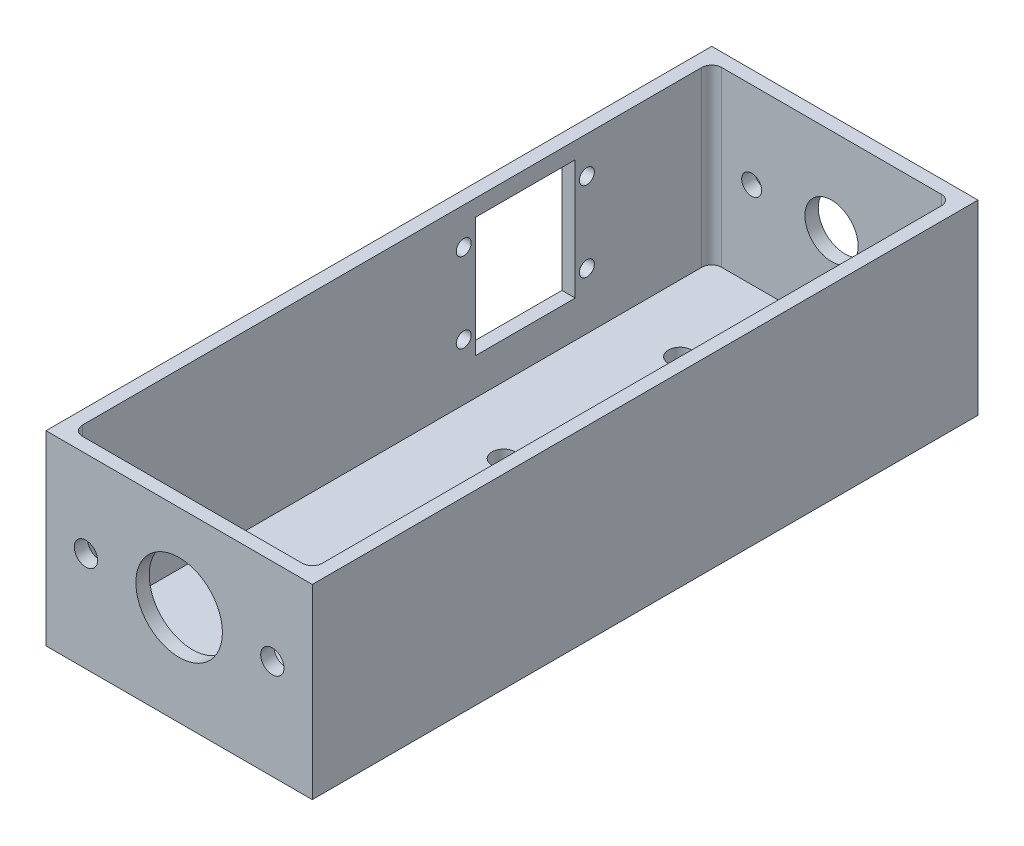
SolidWorks part; units mm, degrees
material "合金钢"
ref_plane "前视基准面" through (0, 0, 0) normal (0, 0, 1) x (1, 0, 0)
ref_plane "上视基准面" through (0, 0, 0) normal (0, 1, 0) x (1, 0, 0)
ref_plane "右视基准面" through (0, 0, 0) normal (1, 0, 0) x (0, 0, -1)
sketch "草图1" plane through (0, 0, 0) normal (0, 0, 1) x (1, 0, 0)
  line L1 (-40, -28) -> (40, -28)
  line L2 (-40, -28) -> (-40, 28)
  line L3 (-40, 28) -> (40, 28)
  line L4 (40, -28) -> (40, 28)
  line L5 (-40, -28) -> (40, 28) construction
  line L6 (-40, 28) -> (40, -28) construction
  point P0 (0, 0)
  dimension "D1" = 80
  dimension "D2" = 56
extrude "凸台-拉伸1" add sketch "草图1" against normal blind 200
sketch "草图2" plane through (0, 28, 0) normal (0, 1, 0) x (1, 0, 0)
  line L0 (-36, 193) -> (-36, 7)
  line L1 (-33, 4) -> (33, 4)
  line L2 (36, 7) -> (36, 193)
  line L3 (33, 196) -> (-33, 196)
  line L4 (-40, 0) -> (40, 0)
  line L5 (40, 0) -> (40, 200)
  line L6 (40, 200) -> (-40, 200)
  line L7 (-40, 200) -> (-40, 0)
  line L8 (-40, 0) -> (40, 0)
  line L9 (40, 0) -> (40, 200)
  line L10 (40, 200) -> (-40, 200)
  line L11 (-40, 200) -> (-40, 0)
  line L12 (-36, 4) -> (36, 4) construction
  line L13 (36, 4) -> (36, 196) construction
  line L14 (-36, 196) -> (-36, 4) construction
  line L15 (36, 196) -> (-36, 196) construction
  arc A0 (33, 4) -> (36, 7) centre (33, 7) ccw
  arc A1 (-36, 7) -> (-33, 4) centre (-33, 7) ccw
  arc A2 (36, 193) -> (33, 196) centre (33, 193) ccw
  arc A3 (-36, 193) -> (-33, 196) centre (-33, 193) cw
  dimension "D3" = 3
  dimension "D1" = 0
  dimension "D2" = 4
extrude "切除-拉伸1" cut sketch "草图2" against normal blind 52 contours A3 L0 A1 L1 A0 L2 A2 L3 region at (0, 28, -100)
sketch "草图3" plane through (0, 0, 0) normal (0, 0, 1) x (1, 0, 0)
  line L0 (0, 0) -> (0, 37.0041) construction
  line L4 (-40, -28) -> (40, -28) construction
  line L5 (40, 28) -> (-40, 28) construction
  line L9 (0, 2) -> (0, 28) construction
  line L10 (-28, 2) -> (28, 2) construction
  circle A0 centre (-28, 2) radius 3.5
  circle A1 centre (0, 2) radius 13
  circle A2 centre (28, 2) radius 3.5
  dimension "D2" = 7
  dimension "D3" = 26
  dimension "D4" = 7
  dimension "D5" = 30
  dimension "D6" = 28
  dimension "D7" = 28
extrude "切除-拉伸2" cut sketch "草图3" against normal blind 10
sketch "草图4" plane through (-40, 0, 0) normal (-1, 0, 0) x (0, 0, 1)
  line L0 (-125, -13) -> (-155, -13)
  line L1 (-125, -13) -> (-125, 23)
  line L2 (-125, 23) -> (-155, 23)
  line L3 (-155, -13) -> (-155, 23)
  line L4 (-140, -1.9135) -> (-140, 22.4271) construction
  line L5 (-200, 28) -> (0, 28) construction
  line L6 (-200, 28) -> (-200, -28) construction
  circle A0 centre (-120, -7) radius 2
  circle A1 centre (-120, 17) radius 2
  circle A2 centre (-160, 17) radius 2
  circle A3 centre (-160, -7) radius 2
  dimension "D1" = 4
  dimension "D2" = 4
  dimension "D3" = 36
  dimension "D4" = 6
  dimension "D5" = 5
  dimension "D6" = 6
  dimension "D7" = 5
  dimension "D8" = 30
  dimension "D9" = 5
  dimension "D10" = 60
extrude "切除-拉伸3" cut sketch "草图4" against normal blind 10 contours L3 L0 L1 L2 region at (-40, 5, -140)
sketch "草图5" plane through (0, 0, -200) normal (0, 0, -1) x (-1, 0, 0)
  line L0 (0, -25.8214) -> (0, 19.1786) construction
  line L1 (0, 28) -> (0, 39.9128) construction
  line L2 (0, 2) -> (24, 2) construction
  line L3 (40, -28) -> (-40, -28) construction
  line L5 (-40, 28) -> (40, 28) construction
  circle A0 centre (0, 2) radius 8
  circle A1 centre (24, 2) radius 3
  circle A2 centre (-24, 2) radius 3
  dimension "D1" = 16
  dimension "D3" = 6
  dimension "D2" = 30
  dimension "D4" = 24
extrude "切除-拉伸4" cut sketch "草图5" against normal blind 10
sketch "草图6" plane through (0, -24, 0) normal (0, 1, 0) x (1, 0, 0)
  line L0 (-16, 113.5) -> (-16, 166.5) construction
  line L1 (-16, 140) -> (-23.7867, 140) construction
  line L2 (-36, 193) -> (-36, 7) construction
  line L4 (-40, 200) -> (40, 200) construction
  circle A0 centre (-16, 166.5) radius 3.5
  circle A1 centre (-16, 113.5) radius 3.5
  dimension "D2" = 7
  dimension "D5" = 7
  dimension "D1" = 53
  dimension "D3" = 20
  dimension "D4" = 60
extrude "切除-拉伸5" cut sketch "草图6" against normal blind 10
sketch "草图8" plane through (-40, 0, 0) normal (-1, 0, 0) x (0, 0, 1)
  line L0 (-140, 23) -> (-140, -13) construction
  line L1 (-125, 23) -> (-155, 23) construction
  line L2 (-155, -13) -> (-125, -13) construction
sketch "草图9" plane through (-40, 0, 0) normal (-1, 0, 0) x (0, 0, 1)
  line L1 (-158.5, -7.0177) -> (-121.5, -7.0177) construction
  line L2 (-121.5, -7.0177) -> (-121.5, 16.9823) construction
  line L4 (0, -28) -> (0, 28)
  line L5 (0, 28) -> (-200, 28)
  line L6 (-200, 28) -> (-200, -28)
  line L7 (-200, -28) -> (0, -28)
  line L8 (0, -28) -> (0, 28)
  line L9 (0, 28) -> (-200, 28)
  line L10 (-200, 28) -> (-200, -28)
  line L11 (-200, -28) -> (0, -28)
  circle A0 centre (-121.5, -7.0177) radius 2.25
  circle A1 centre (-158.5, -7.0177) radius 2.25
  circle A2 centre (-158.5, 16.9823) radius 2.25
  circle A3 centre (-121.5, 16.9823) radius 2.25
  dimension "D2" = 4.5
  dimension "D5" = 24
  dimension "D6" = 37
  dimension "D1" = 0
  dimension "D3" = 2
  dimension "D4" = 2
extrude "切除-拉伸6" cut sketch "草图9" against normal blind 10 contours A2 | A1 | A0 | A3
